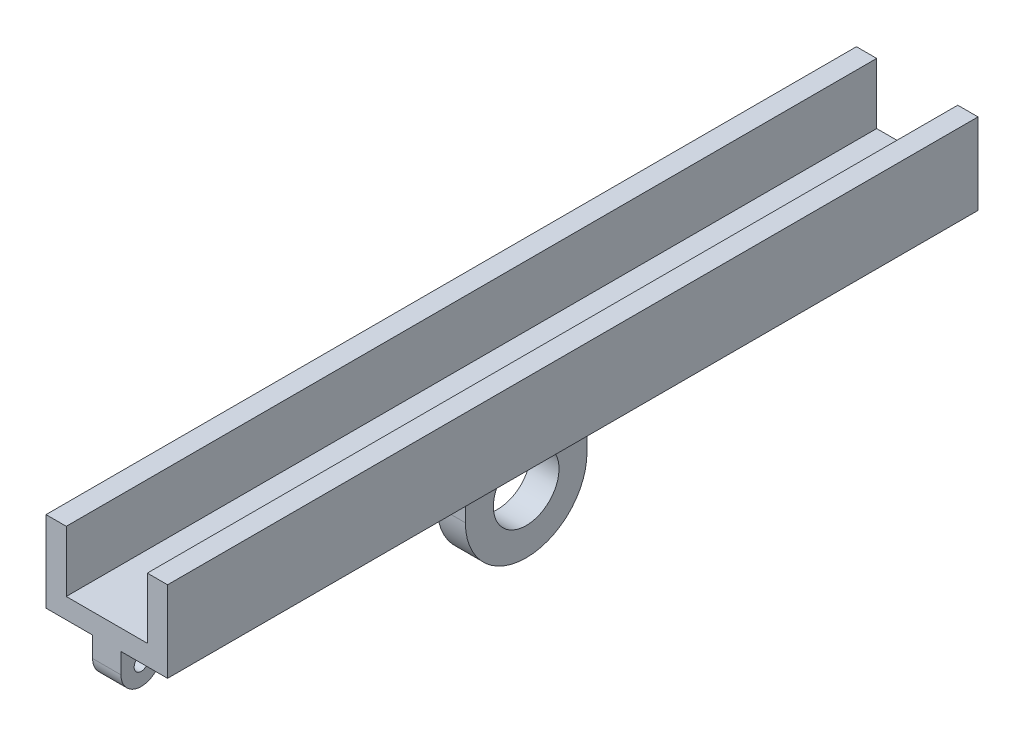
SolidWorks part; units mm, degrees
ref_plane "Front Plane" through (0, 0, 0) normal (0, 0, 1) x (1, 0, 0)
ref_plane "Top Plane" through (0, 0, 0) normal (0, 1, 0) x (1, 0, 0)
ref_plane "Right Plane" through (0, 0, 0) normal (1, 0, 0) x (0, 0, -1)
sketch "Sketch1" plane through (0, 0, 0) normal (0, 0, 1) x (1, 0, 0)
  line L0 (25, 20) -> (30, 20)
  line L1 (0, 0) -> (30, 0)
  line L2 (0, 0) -> (0, 20)
  line L3 (0, 20) -> (5, 20)
  line L4 (30, 0) -> (30, 20)
  line L6 (5, 20) -> (5, 5)
  line L7 (5, 5) -> (25, 5)
  line L8 (25, 20) -> (25, 5)
  dimension "D1" = 20
  dimension "D2" = 5
  dimension "D3" = 5
  dimension "D4" = 5
  dimension "D5" = 15
extrude "Boss-Extrude1" add sketch "Sketch1" along normal blind 200
sketch "Sketch2" plane through (30, 0, 0) normal (1, 0, 0) x (0, 0, -1)
  line L5 (-200, 0) -> (0, 0) construction
  line L6 (-115, -15) -> (-115, -10)
  line L7 (-85, -15) -> (-85, -10)
  line L10 (-125, 0) -> (-75, 0)
  circle A0 centre (-100, -15) radius 8.1
  arc A1 (-115, -15) -> (-85, -15) centre (-100, -15) ccw
  arc A2 (-85, -10) -> (-75, 0) centre (-75, -10) cw
  arc A3 (-115, -10) -> (-125, 0) centre (-125, -10) ccw
  point P4 (-100, 0)
  point P11 (-85, 0)
  point P14 (-115, 0)
  dimension "D2" = 16.2
  dimension "D3" = 10
  dimension "D4" = 15
  dimension "D1" = 15
  dimension "D5" = 50
extrude "Boss-Extrude2" add sketch "Sketch2" against normal blind 7 from offset 11.5 offset against normal yes
sketch "Sketch3" plane through (30, 0, 0) normal (1, 0, 0) x (0, 0, -1)
  line L1 (-200, 0) -> (-190, 0)
  line L2 (-200, 0) -> (-200, -10)
  line L3 (-200, -10) -> (-190, -10)
  line L4 (-190, 0) -> (-190, -10)
  circle A0 centre (-195, -5) radius 1.75
  dimension "D2" = 3.5
  dimension "D1" = 5
  dimension "D3" = 5
  dimension "D4" = 10
  dimension "D5" = 10
extrude "Boss-Extrude3" add sketch "Sketch3" along normal blind 7 from offset 18.5 offset against normal yes
fillet "Fillet1" radius 5 2 edges at (15, -10, 190) (15, -10, 200)
sketch "Sketch5" plane through (0, 5, 0) normal (0, 1, 0) x (1, 0, 0)
  line L0 (25, -200) -> (5, -200) construction
  line L1 (5, -100) -> (25, -100) construction
  line L2 (5, -200) -> (5, 0) construction
  line L3 (25, -200) -> (25, 0) construction
  circle A0 centre (15, -180) radius 1.5
  circle A1 centre (15, -160) radius 1.5
  circle A2 centre (15, -40) radius 1.5
  circle A3 centre (15, -20) radius 1.5
  point P8 (15, -200)
  dimension "D3" = 3
  dimension "D1" = 20
  dimension "D2" = 20
extrude "Cut-Extrude1" cut sketch "Sketch5" against normal blind 7
